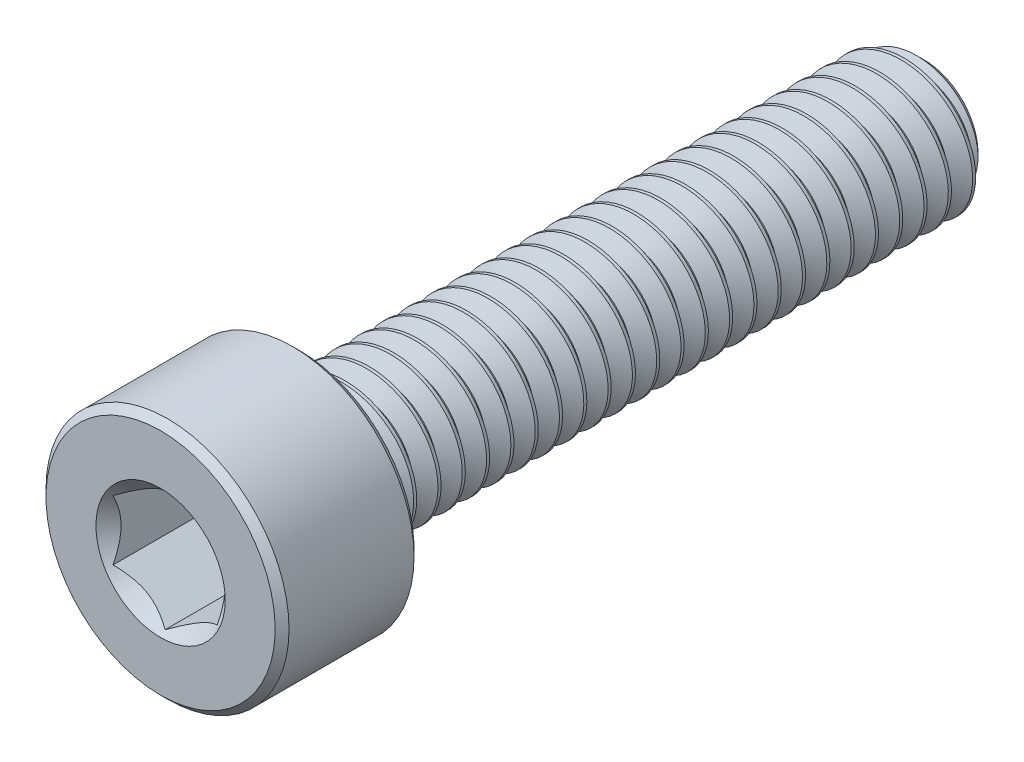
SolidWorks part; units mm, degrees
ref_plane "Front Plane" through (0, 0, 0) normal (0, 0, 1) x (1, 0, 0)
ref_plane "Top Plane" through (0, 0, 0) normal (0, 1, 0) x (1, 0, 0)
ref_plane "Right Plane" through (0, 0, 0) normal (1, 0, 0) x (0, 0, -1)
sketch "Sketch1" plane through (0, 0, 0) normal (1, 0, 0) x (0, 0, -1)
  line L0 (-11, 0) -> (11, 0) construction
  line L1 (11, 0) -> (11, 1.5453) construction
  line L2 (11, 1.5453) -> (10.5453, 2) construction
  line L3 (10.5453, 2) -> (10.475, 2) construction
  line L4 (10.475, 2) -> (-7, 2) construction
  line L5 (-7, 2) -> (-7, 3.5) construction
  line L6 (-7, 3.5) -> (-11, 3.5) construction
  line L7 (-11, 3.5) -> (-11, 0) construction
  line L8 (11, 1.5453) -> (11, 2) construction
  line L9 (10.9563, 2.0758) -> (11.3063, 1.4696) construction
  line L10 (11.3063, 1.4696) -> (11.6563, 2.0758) construction
  line L11 (11.6563, 2.0758) -> (10.9563, 2.0758) construction
  line L12 (11.3063, 2.0758) -> (11.3063, 2) construction
  line L13 (11.3063, 1.4696) -> (11.3063, 1.5453) construction
  line L14 (11.2625, 1.5453) -> (11.35, 1.5453) construction
  line L15 (11, 2) -> (11.6125, 2) construction
  line L16 (10.9781, 2.0379) -> (11.6344, 2.0379) construction
  line L17 (11, 0) -> (11, -2) construction
  line L18 (-7.2, 3.5) -> (-7, 3.3) construction
  line L19 (-10.8, 3.5) -> (-11, 3.3) construction
  line L20 (-7, 2) -> (-7, 0) construction
  line L21 (-7, 1) -> (-1, 1) construction
  line L22 (-1, 1) -> (5, 1) construction
  line L23 (5, 1) -> (11, 1) construction
  line L24 (-1, 1) -> (-1, 2) construction
  line L25 (-1, 2) -> (-1, 3.5) construction
  line L26 (5, 1) -> (5, 3.5) construction
  point P0 (-11, 1.5)
  point P3 (9.25, 2)
  point P4 (0, 0)
  point P18 (5, 2)
  point P22 (11.3063, 1.5453)
  point P24 (10.475, 2)
  point P25 (11.3063, 2)
  point P28 (11.3063, 2.0379)
  point P29 (9.25, -2)
  point P30 (-1, 2)
  point P31 (-9, 3.5)
  point P37 (-7.7, 3.5)
  point P38 (-10.7, 3.5)
  point P45 (-1, 1)
  point P46 (5, 1)
  dimension "D2" = 0.0875
  dimension "D7" = 0.2
  dimension "D8" = 0.2
  dimension "D9" = 0.2
  dimension "D10" = 0.1
  dimension "D11" = 0.5
  dimension "Drive Size" = 3
  dimension "Head Diameter" = 7
  dimension "Head Height" = 4
  dimension "Thread Pitch" = 0.7
  dimension "Thread Dia" = 4
  dimension "Length" = 18
  dimension "D12" = 0.525
  dimension "D4" = 1.75
  dimension "D3" = 45
sketch "Sketch2" plane through (0, 0, 0) normal (1, 0, 0) x (0, 0, -1)
  line L0 (-11, 0) -> (-11, 3.3)
  line L1 (-10.8, 3.5) -> (-7.2, 3.5)
  line L2 (-7, 3.3) -> (-7, 2.2)
  line L4 (10.5453, 2) -> (11, 1.5453)
  line L5 (11, 1.5453) -> (11, 0)
  line L6 (-7, 3.5) -> (-11, 3.5) construction
  line L7 (11, 0) -> (-11, 0)
  line L8 (-10.8, 3.5) -> (-11, 3.3) construction
  line L10 (-10.8, 3.5) -> (-11, 3.3)
  line L14 (-7.2, 3.5) -> (-7, 3.3) construction
  line L16 (-7.2, 3.5) -> (-7, 3.3)
  line L17 (-7, 2) -> (-7, 3.5) construction
  line L19 (-6.8, 2) -> (10.5453, 2)
  line L20 (10.475, 2) -> (-7, 2) construction
  arc A1 (-7, 2.2) -> (-6.8, 2) centre (-6.8, 2.2) ccw
  dimension "D3" = 0.2
revolve "Revolve1" add sketch "Sketch2" angle 360 about L7
sketch "Sketch3" plane through (0, 0, 11) normal (0, 0, 1) x (1, 0, 0)
  line L1 (1.5, -0.866) -> (1.5, 0.866)
  line L2 (1.5, 0.866) -> (0, 1.7321)
  line L3 (0, 1.7321) -> (-1.5, 0.866)
  line L4 (-1.5, 0.866) -> (-1.5, -0.866)
  line L5 (-1.5, -0.866) -> (0, -1.7321)
  line L6 (0, -1.7321) -> (1.5, -0.866)
  circle A0 centre (0, 0) radius 1.5 construction
  circle A1 centre (0, 0) radius 3.5 construction
  circle A2 centre (0, 0) radius 3.5 construction
  circle A3 centre (0, 0) radius 1.7321 construction
  point P13 (0, 0)
  dimension "D1" = 3.4641
extrude "Cut-Extrude1" cut sketch "Sketch3" against normal offset from surface (3 mm away) 1 up to face at (0, 3.3, 7)
sketch "Sketch4" plane through (0, 0, 11) normal (0, 0, 1) x (1, 0, 0)
  circle A0 centre (0, 0) radius 1.862
  dimension "D1" = 3.7239
extrude "Cut-Extrude2" cut sketch "Sketch4" against normal up to vertex (2 mm away) draft 45 up to point (0, 3.5, 9)
sketch "Sketch11" plane through (0, 0, 0) normal (1, 0, 0) x (0, 0, -1)
  line L0 (-11, 0) -> (11, 0) construction
  line L1 (-11, 0) -> (11, 0) construction
  line L2 (-3.625, 0) -> (-3.625, 2) construction
  line L3 (10.475, 2) -> (-7, 2) construction
  line L4 (7.625, 0) -> (7.625, 2) construction
  line L6 (11, 1.5453) -> (11, 2) construction
  point P2 (-3.625, 0)
  point P3 (7.625, 0)
  dimension "D1" = 3.375
  dimension "D2" = 3.375
sketch "Sketch6" plane through (0, 0, -11) normal (0, 0, -1) x (-1, 0, 0)
  circle A0 centre (0, 0) radius 2
curve "Helix/Spiral1" pitch 0.7 height 18.7 turns 26.7143
sketch "Sketch10" plane through (0, 0, 0) normal (1, 0, 0) x (0, 0, -1)
  line L0 (-6.8, -3.5) -> (-6.8, 3.5)
  line L5 (-11, 0) -> (11, 0) construction
  line L6 (-6.8, 2) -> (-6.8, -2) construction
  point P3 (-6.8, 0)
split "Split1" trim tools "Sketch10" bodies to split 106 resulting bodies 114 115
sketch "Sketch7" plane through (0, 0, 0) normal (1, 0, 0) x (0, 0, -1)
  line L0 (10.9781, 2.0379) -> (11.6344, 2.0379)
  line L1 (11.6344, 2.0379) -> (11.35, 1.5453)
  line L2 (11.35, 1.5453) -> (11.2625, 1.5453)
  line L3 (11.2625, 1.5453) -> (10.9781, 2.0379)
sweep "Cut-Sweep1" cut profiles "Sketch7" path "Helix/Spiral1" align with end faces yes
sketch "Sketch8" plane through (0, 0, 0) normal (1, 0, 0) x (0, 0, -1)
  line L0 (-7, 0) -> (-7, 2)
  line L1 (-6.8, -2) -> (-6.8, 2) construction
  line L2 (-7, 2) -> (-6.8, 2)
  line L4 (-6.8, 2) -> (-5.6453, 0)
  line L5 (-5.6453, 0) -> (-7, 0)
  line L6 (10.475, 2) -> (-7, 2) construction
  line L7 (-11, 0) -> (11, 0) construction
  dimension "D1" = 60
revolve "Revolve2" add sketch "Sketch8" angle 360 about L5
equation "\"D2@Sketch1\" = \"Thread Pitch@Sketch1\" / 8"
equation "\"D4@Helix/Spiral1\" = \"Thread Pitch@Sketch1\""
equation "\"D7@Sketch1\" = \"Head Height@Sketch1\" * .05"
equation "\"D8@Sketch1\"=\"D7@Sketch1\""
equation "\"D9@Sketch1\"=\"D7@Sketch1\""
equation "\"D10@Sketch1\"=\"D7@Sketch1\"/2"
equation "\"D11@Sketch1\"=\"D10@Sketch1\"*5"
equation "\"D4@Sketch1\"=\"Thread Pitch@Sketch1\"*2.5"
equation "\"D12@Sketch1\"=\"Thread Pitch@Sketch1\"*.75"
equation "\"D3@Helix/Spiral1\"=\"Length@Sketch1\"+\"Thread Pitch@Sketch1\""
equation "\"D3@Sketch2\"=\"Thread Dia@Sketch1\"*0.05"
equation "\"D1@Sketch11\"=\"Length@Sketch1\"*0.1875"
equation "\"D2@Sketch11\"=\"D1@Sketch11\""
equation "\"D1@Sketch4\"=\"D1@Sketch3\"*1.075"
